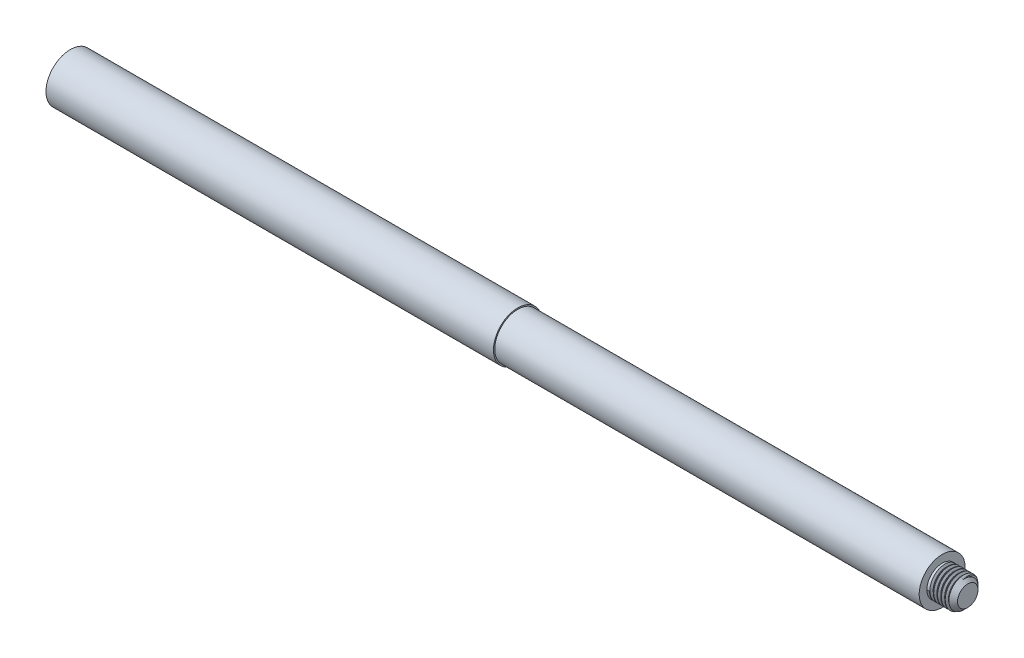
SolidWorks part; units mm, degrees
ref_plane "Płaszczyzna przednia" through (0, 0, 0) normal (0, 0, 1) x (1, 0, 0)
ref_plane "Płaszczyzna górna" through (0, 0, 0) normal (0, 1, 0) x (1, 0, 0)
ref_plane "Płaszczyzna prawa" through (0, 0, 0) normal (1, 0, 0) x (0, 0, -1)
sketch "Szkic1" plane through (0, 0, 0) normal (1, 0, 0) x (0, 0, -1)
  circle A0 centre (0, 0) radius 9
  dimension "D1" = 18
extrude "Dodanie-wyciągnięcie1" add sketch "Szkic1" along normal blind 166
sketch "Szkic2" plane through (0, 0, 0) normal (-1, 0, 0) x (0, 0, 1)
  circle A0 centre (0, 0) radius 9.5
  dimension "D1" = 19
extrude "Dodanie-wyciągnięcie2" add sketch "Szkic2" along normal blind 175
sketch "Szkic3" plane through (166, 0, 0) normal (1, 0, 0) x (0, 0, -1)
  circle A0 centre (0, 0) radius 6
  dimension "D1" = 12
extrude "Dodanie-wyciągnięcie3" add sketch "Szkic3" along normal blind 10
sketch "Szkic10" plane through (0, 0, 0) normal (0, 0, 1) x (1, 0, 0)
  line L1 (-175, 0) -> (166, 0) construction
  line L2 (-175, 9.5) -> (-175, -9.5) construction
  line L3 (166, -6) -> (166, 6) construction
  line L4 (-4.5, 0) -> (-4.5, 14.6263) construction
  point P9 (-4.5, 9.5)
  point P10 (-4.5, 14.6263)
chamfer "Sfazowanie1" distance 2 angle 45 1 edges at (176, 0, -6)
thread "Gwint2" pitch 1.5 method cut profile "Profil gwintu2" start angle 0, offset 5, length 12, pitch 1.5, diameter 12
ref_plane "Płaszczyzna2" through (179, 0, 6) normal (0, -1, 0) x (0, 0, 1)
sketch "Profil gwintu2" plane through (179, 0, 6) normal (0, -1, 0) x (0, 0, 1)
  line L0 (0, 0) -> (0, 1.5) construction
  line L11 (0, 0) -> (0, 1.3125)
  line L12 (0, 1.3125) -> (-0.8119, 0.8437)
  line L13 (-0.8119, 0.8437) -> (-0.8119, 0.4687)
  line L15 (-0.8119, 0.4687) -> (0, 0)
  line L17 (-0.8119, 0.6562) -> (0, 0.6562) construction
  point P2 (0, 0)
  dimension "Pitch" = 1.5
  dimension "Profile_Angle" = 60
  dimension "Profile_Land" = 0.375
  dimension "Profile_Height" = 0.8119
